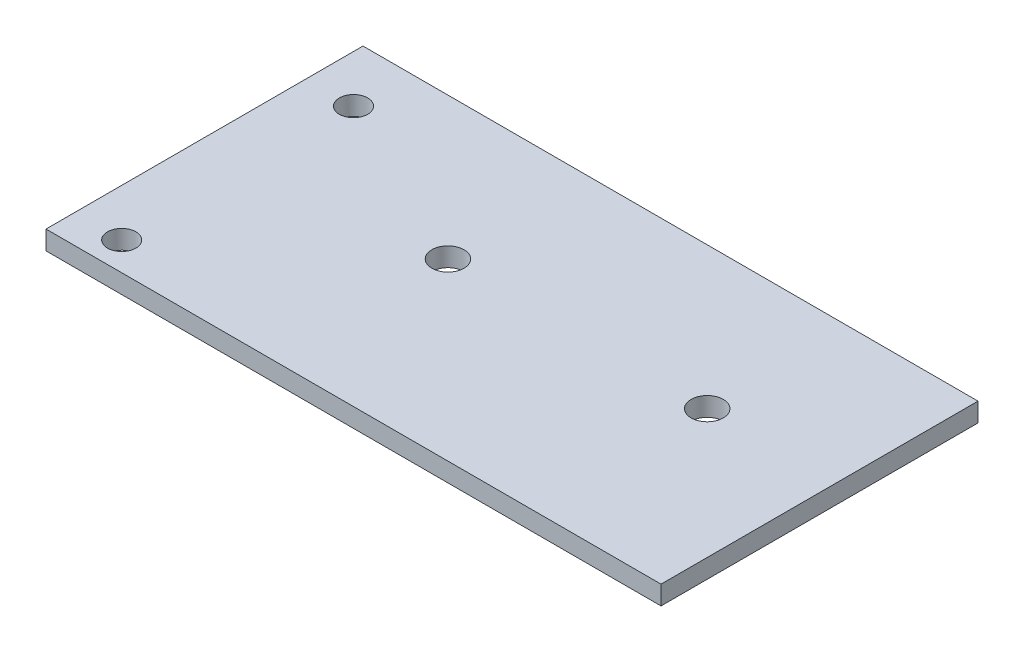
SolidWorks part; units mm, degrees
ref_plane "Front Plane" through (0, 0, 0) normal (0, 0, 1) x (1, 0, 0)
ref_plane "Top Plane" through (0, 0, 0) normal (0, 1, 0) x (1, 0, 0)
ref_plane "Right Plane" through (0, 0, 0) normal (1, 0, 0) x (0, 0, -1)
sketch "Sketch1" plane through (0, 0, 0) normal (0, 1, 0) x (1, 0, 0)
  line L1 (-84.8661, 30.4945) -> (-19.8661, 30.4945)
  line L2 (-84.8661, 30.4945) -> (-84.8661, -3.0055)
  line L3 (-84.8661, -3.0055) -> (-19.8661, -3.0055)
  line L4 (-19.8661, 30.4945) -> (-19.8661, -3.0055)
  dimension "D1" = 33.5
  dimension "D2" = 65
extrude "Boss-Extrude1" add sketch "Sketch1" along normal blind 2
hole_wizard "M3 Clearance Hole4" positions "Sketch12" profile "Sketch13" hole size "M3" standard "ANSI Metric" end condition through all
sketch "Sketch12" plane through (0, 0, 0) normal (0, -1, 0) x (-1, 0, 0)
  circle A0 centre (33.4861, 15.4945) radius 1.25 construction
  circle A1 centre (60.8861, 15.4945) radius 1.25 construction
  point P0 (33.4861, 15.4945)
  point P15 (60.8861, 15.4945)
sketch "Sketch13" plane through (-33.4861, 0, -15.4945) normal (1, 0, 0) x (0, 0, -1)
  line L0 (0, 0) -> (0, 2)
  line L1 (0, 2) -> (1.7, 2)
  line L2 (1.7, 2) -> (1.7, 0)
  line L5 (1.7, 0) -> (0, 0)
  line L11 (0, -6.35) -> (0, 107.95) construction
  dimension "Thru Hole Dia." = 3.4
  dimension "Thru Hole Depth" = 2
sketch "Sketch6" plane through (0, 0, 0) normal (0, 1, 0) x (1, 0, 0)
  line L0 (-84.8661, -3.0055) -> (-19.8661, -3.0055) construction
  line L1 (-71.1161, -3.0055) -> (-69.1161, -3.0055)
  line L2 (-71.1161, -3.0055) -> (-71.1161, 30.4945)
  line L3 (-71.1161, 30.4945) -> (-69.1161, 30.4945)
  line L4 (-69.1161, -3.0055) -> (-69.1161, 30.4945)
  line L5 (-19.8661, 30.4945) -> (-84.8661, 30.4945) construction
  line L7 (-33.6161, -3.0055) -> (-35.6161, -3.0055)
  line L8 (-33.6161, -3.0055) -> (-33.6161, 30.4945)
  line L9 (-33.6161, 30.4945) -> (-35.6161, 30.4945)
  line L10 (-35.6161, -3.0055) -> (-35.6161, 30.4945)
  line L11 (-52.3661, 30.4945) -> (-52.3661, -3.0055) construction
  line L12 (-19.8661, 30.4945) -> (-84.8661, 30.4945) construction
  line L13 (-84.8661, -3.0055) -> (-19.8661, -3.0055) construction
  dimension "D1" = 33.5
  dimension "D3" = 2
extrude "Boss-Extrude2" [suppressed] add sketch "Sketch6" against normal blind 10
hole_wizard "M3x0.5 Tapped Hole1" positions "3DSketch2" profile "Sketch11" tap size "M3x0.5" standard "ANSI Metric"
sketch3d "3DSketch2"
  circle A0 centre (-79.8661, 35.5, 0.0055) radius 1.25 construction
  circle A1 centre (-79.8661, 31.45, -24.4945) radius 1.25 construction
  point P36 (-79.8661, 0, 0.0055)
  point P38 (-79.8661, 0, -24.4945)
  point P44 (-79.8661, 36.75, 0.0055)
  point P48 (-79.8661, 32.7, -24.4945)
sketch "Sketch11" plane through (-79.8661, 0, 0.0055) normal (1, 0, 0) x (0, 0, -1)
  line L0 (0, 0) -> (0, 10.7511)
  line L1 (0, 10.7511) -> (1.25, 10)
  line L2 (1.25, 10) -> (1.25, 6)
  line L3 (1.25, 6) -> (1.5, 6)
  line L4 (1.5, 6) -> (1.5, 0)
  line L5 (1.5, 0) -> (0, 0)
  line L10 (0, 10.7511) -> (-1.25, 10) construction
  line L11 (0, -6.35) -> (0, 107.95) construction
  dimension "Tap Drill Dia." = 2.5
  dimension "Tap Drill Depth" = 10
  dimension "Thread Major Dia." = 3
  dimension "Thread Depth" = 6
  dimension "Drill Angle" = 118
